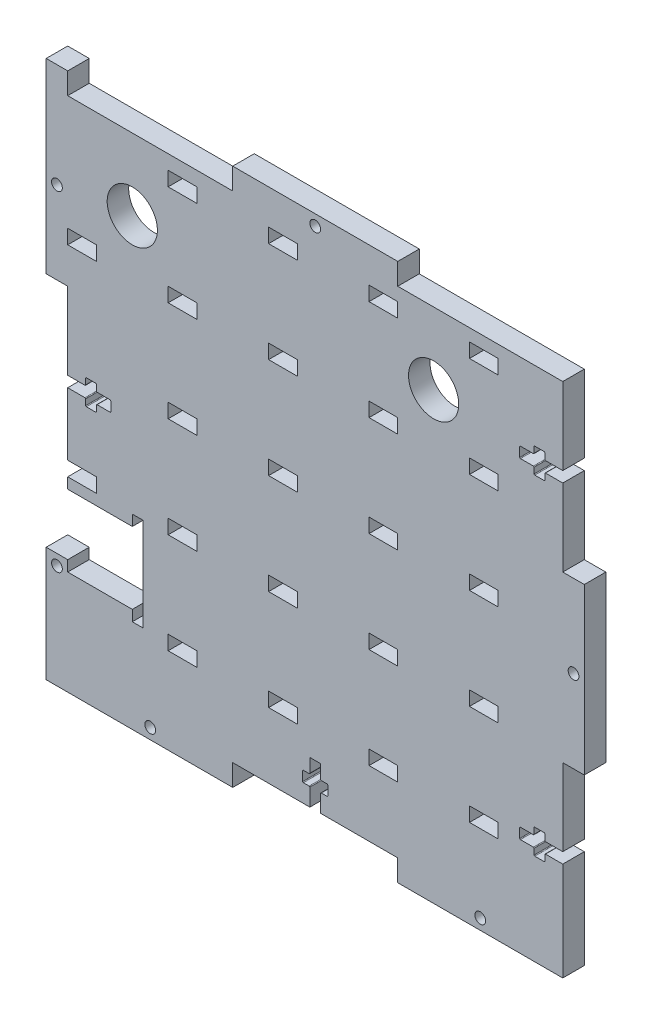
SolidWorks part; units mm, degrees
ref_plane "Front Plane" through (0, 0, 0) normal (0, 0, 1) x (1, 0, 0)
ref_plane "Top Plane" through (0, 0, 0) normal (0, 1, 0) x (1, 0, 0)
ref_plane "Right Plane" through (0, 0, 0) normal (1, 0, 0) x (0, 0, -1)
sketch "Sketch1" plane through (0, 0, 0) normal (0, 0, 1) x (1, 0, 0)
  line L0 (-69, 69) -> (-23, 69)
  line L5 (-75, -75) -> (75, -75) construction
  line L6 (-75, -75) -> (-75, 75) construction
  line L7 (-75, 75) -> (75, 75) construction
  line L8 (75, -75) -> (75, 75) construction
  line L9 (75, 23) -> (69, 23)
  line L10 (69, -23) -> (75, -23)
  line L11 (-69, -69) -> (69, -69) construction
  line L12 (-69, -69) -> (-69, 69) construction
  line L13 (-69, 69) -> (69, 69) construction
  line L14 (69, -69) -> (69, 69) construction
  line L15 (-69, -69) -> (69, 69) construction
  line L16 (69, -69) -> (69, -23)
  line L17 (-23, 69) -> (-23, 75)
  line L18 (-23, 75) -> (23, 75)
  line L19 (23, 75) -> (23, 69)
  line L20 (23, 69) -> (69, 69)
  line L21 (75, -23) -> (75, 23)
  line L22 (69, 23) -> (69, 69)
  line L23 (-75, 23) -> (-69, 23)
  line L24 (-69, 69) -> (-75, 69)
  line L25 (-75, 69) -> (-75, 23)
  line L26 (69, -69) -> (69, -75)
  line L27 (69, -75) -> (23, -75)
  line L28 (23, -75) -> (23, -69)
  line L29 (23, -69) -> (-23, -69)
  line L30 (-23, -69) -> (-23, -75)
  line L31 (-23, -75) -> (-69, -75)
  line L32 (-69, -75) -> (-69, -69) construction
  line L33 (-69, 23) -> (-69, -23)
  line L34 (-69, -23) -> (-75, -23)
  line L35 (-75, -23) -> (-75, -69)
  line L36 (-75, -69) -> (-69, -69) construction
  line L37 (-46, 69) -> (-46, -75) construction
  line L38 (-69, 69) -> (69, -69) construction
  line L39 (-75, -75) -> (-69, -75)
  line L40 (-75, -75) -> (-75, -69)
  point P0 (0, 0)
  point P6 (-7, -7)
  point P26 (0, -75)
  point P27 (-75, 0)
  dimension "D1" = 150
  dimension "D2" = 150
  dimension "D5" = 46
  dimension "D3" = 6
  dimension "D6" = 6
  dimension "D7" = 6
extrude "Box Side" add sketch "Sketch1" along normal blind 6
sketch "Sketch2" plane through (0, 0, 6) normal (0, 0, 1) x (1, 0, 0)
  line L0 (23, 72) -> (-23, 72) construction
  line L1 (23, 75) -> (23, 69) construction
  line L2 (-23, 69) -> (-23, 75) construction
  line L3 (-46, 69) -> (-46, -75) construction
  line L5 (0, 75) -> (0, 69) construction
  line L6 (-23, 75) -> (23, 75) construction
  line L7 (-69, 69) -> (69, 69) construction
  line L16 (-46, 69) -> (-46, -75) construction
  line L21 (0, -69) -> (0, 69) construction
  line L35 (-69, 69) -> (-23, 69) construction
  line L36 (-44.5, 69) -> (-44.5, 64.2) construction
  line L37 (-44.3, 64) -> (-42.7, 64) construction
  line L38 (-42.5, 63.8) -> (-42.5, 61.2) construction
  line L39 (-42.7, 61) -> (-44.3, 61) construction
  line L40 (-44.5, 60.8) -> (-44.5, 57.2) construction
  line L46 (-44.7, 57) -> (-47.3, 57) construction
  line L48 (-44.5, 69) -> (-47.5, 69) construction
  line L51 (-47.5, 60.8) -> (-47.5, 57.2) construction
  line L52 (-49.3, 61) -> (-47.7, 61) construction
  line L53 (-49.5, 63.8) -> (-49.5, 61.2) construction
  line L54 (-47.7, 64) -> (-49.3, 64) construction
  line L55 (-47.5, 69) -> (-47.5, 64.2) construction
  line L56 (47.5, 69) -> (47.5, 64.2) construction
  line L57 (47.7, 64) -> (49.3, 64) construction
  line L58 (49.5, 63.8) -> (49.5, 61.2) construction
  line L59 (49.3, 61) -> (47.7, 61) construction
  line L60 (47.5, 60.8) -> (47.5, 57.2) construction
  line L61 (44.5, 69) -> (47.5, 69) construction
  line L62 (44.7, 57) -> (47.3, 57) construction
  line L63 (44.5, 60.8) -> (44.5, 57.2) construction
  line L64 (42.7, 61) -> (44.3, 61) construction
  line L65 (42.5, 63.8) -> (42.5, 61.2) construction
  line L66 (44.3, 64) -> (42.7, 64) construction
  line L67 (44.5, 69) -> (44.5, 64.2) construction
  line L68 (-69, -69) -> (69, 69) construction
  line L69 (-69, -69) -> (69, 69) construction
  line L70 (75, 0) -> (69, 0) construction
  line L71 (72, 23) -> (72, -23) construction
  line L72 (69, 44.5) -> (64.2, 44.5)
  line L73 (64, 44.3) -> (64, 42.7)
  line L74 (63.8, 42.5) -> (61.2, 42.5)
  line L75 (61, 42.7) -> (61, 44.3)
  line L76 (60.8, 44.5) -> (57.2, 44.5)
  line L77 (57, 44.7) -> (57, 47.3)
  line L78 (69, 44.5) -> (69, 47.5)
  line L79 (60.8, 47.5) -> (57.2, 47.5)
  line L80 (61, 49.3) -> (61, 47.7)
  line L81 (63.8, 49.5) -> (61.2, 49.5)
  line L82 (64, 47.7) -> (64, 49.3)
  line L83 (69, 47.5) -> (64.2, 47.5)
  line L84 (69, -47.5) -> (64.2, -47.5)
  line L85 (64, -47.7) -> (64, -49.3)
  line L86 (63.8, -49.5) -> (61.2, -49.5)
  line L87 (61, -49.3) -> (61, -47.7)
  line L88 (60.8, -47.5) -> (57.2, -47.5)
  line L89 (69, -44.5) -> (69, -47.5)
  line L90 (57, -44.7) -> (57, -47.3)
  line L91 (60.8, -44.5) -> (57.2, -44.5)
  line L92 (61, -42.7) -> (61, -44.3)
  line L93 (63.8, -42.5) -> (61.2, -42.5)
  line L94 (64, -44.3) -> (64, -42.7)
  line L95 (69, -44.5) -> (64.2, -44.5)
  line L120 (-69, 69) -> (69, -69) construction
  line L121 (-69, 69) -> (69, -69) construction
  line L122 (-1.5, -69) -> (1.5, -69)
  line L123 (-23, -69) -> (23, -69) construction
  line L124 (1.5, -69) -> (1.5, -64.2)
  line L125 (1.7, -64) -> (3.3, -64)
  line L126 (3.5, -63.8) -> (3.5, -61.2)
  line L127 (3.3, -61) -> (1.7, -61)
  line L128 (1.5, -60.8) -> (1.5, -57.2)
  line L129 (1.3, -57) -> (-1.3, -57)
  line L130 (-1.5, -60.8) -> (-1.5, -57.2)
  line L131 (-3.3, -61) -> (-1.7, -61)
  line L132 (-3.5, -63.8) -> (-3.5, -61.2)
  line L133 (-1.7, -64) -> (-3.3, -64)
  line L134 (-1.5, -69) -> (-1.5, -64.2)
  line L135 (-69, -1.5) -> (-64.2, -1.5)
  line L136 (-64, -1.7) -> (-64, -3.3)
  line L137 (-63.8, -3.5) -> (-61.2, -3.5)
  line L138 (-61, -3.3) -> (-61, -1.7)
  line L139 (-60.8, -1.5) -> (-57.2, -1.5)
  line L140 (-57, 1.3) -> (-57, -1.3)
  line L141 (-60.8, 1.5) -> (-57.2, 1.5)
  line L142 (-61, 3.3) -> (-61, 1.7)
  line L143 (-63.8, 3.5) -> (-61.2, 3.5)
  line L144 (-64, 1.7) -> (-64, 3.3)
  line L145 (-69, 1.5) -> (-64.2, 1.5)
  line L146 (-69, -1.5) -> (-69, 1.5)
  line L147 (-69, -72) -> (-23, -72) construction
  line L148 (-23, 69) -> (-75, 69) construction
  line L149 (-23, -75) -> (-23, -69) construction
  line L150 (-69, -69) -> (-69, -75) construction
  line L151 (-75, -75) -> (-23, -75) construction
  circle A0 centre (0, 72) radius 1.5
  arc A1 (-44.5, 57.2) -> (-44.7, 57) centre (-44.7, 57.2) cw construction
  arc A2 (-44.3, 61) -> (-44.5, 60.8) centre (-44.3, 60.8) ccw construction
  arc A3 (-42.5, 61.2) -> (-42.7, 61) centre (-42.7, 61.2) cw construction
  arc A4 (-42.7, 64) -> (-42.5, 63.8) centre (-42.7, 63.8) cw construction
  arc A5 (-44.5, 64.2) -> (-44.3, 64) centre (-44.3, 64.2) ccw construction
  arc A6 (-47.5, 64.2) -> (-47.7, 64) centre (-47.7, 64.2) cw construction
  arc A7 (-49.3, 64) -> (-49.5, 63.8) centre (-49.3, 63.8) ccw construction
  arc A8 (-49.5, 61.2) -> (-49.3, 61) centre (-49.3, 61.2) ccw construction
  arc A9 (-47.7, 61) -> (-47.5, 60.8) centre (-47.7, 60.8) cw construction
  arc A10 (-47.5, 57.2) -> (-47.3, 57) centre (-47.3, 57.2) ccw construction
  arc A11 (47.5, 57.2) -> (47.3, 57) centre (47.3, 57.2) cw construction
  arc A12 (47.7, 61) -> (47.5, 60.8) centre (47.7, 60.8) ccw construction
  arc A13 (49.5, 61.2) -> (49.3, 61) centre (49.3, 61.2) cw construction
  arc A14 (49.3, 64) -> (49.5, 63.8) centre (49.3, 63.8) cw construction
  arc A15 (47.5, 64.2) -> (47.7, 64) centre (47.7, 64.2) ccw construction
  arc A16 (44.5, 64.2) -> (44.3, 64) centre (44.3, 64.2) cw construction
  arc A17 (42.7, 64) -> (42.5, 63.8) centre (42.7, 63.8) ccw construction
  arc A18 (42.5, 61.2) -> (42.7, 61) centre (42.7, 61.2) ccw construction
  arc A19 (44.3, 61) -> (44.5, 60.8) centre (44.3, 60.8) cw construction
  arc A20 (44.5, 57.2) -> (44.7, 57) centre (44.7, 57.2) ccw construction
  arc A21 (57.2, 44.5) -> (57, 44.7) centre (57.2, 44.7) cw
  arc A22 (61, 44.3) -> (60.8, 44.5) centre (60.8, 44.3) ccw
  arc A23 (61.2, 42.5) -> (61, 42.7) centre (61.2, 42.7) cw
  arc A24 (64, 42.7) -> (63.8, 42.5) centre (63.8, 42.7) cw
  arc A25 (64.2, 44.5) -> (64, 44.3) centre (64.2, 44.3) ccw
  arc A26 (64.2, 47.5) -> (64, 47.7) centre (64.2, 47.7) cw
  arc A27 (64, 49.3) -> (63.8, 49.5) centre (63.8, 49.3) ccw
  arc A28 (61.2, 49.5) -> (61, 49.3) centre (61.2, 49.3) ccw
  arc A29 (61, 47.7) -> (60.8, 47.5) centre (60.8, 47.7) cw
  arc A30 (57.2, 47.5) -> (57, 47.3) centre (57.2, 47.3) ccw
  arc A31 (57.2, -47.5) -> (57, -47.3) centre (57.2, -47.3) cw
  arc A32 (61, -47.7) -> (60.8, -47.5) centre (60.8, -47.7) ccw
  arc A33 (61.2, -49.5) -> (61, -49.3) centre (61.2, -49.3) cw
  arc A34 (64, -49.3) -> (63.8, -49.5) centre (63.8, -49.3) cw
  arc A35 (64.2, -47.5) -> (64, -47.7) centre (64.2, -47.7) ccw
  arc A36 (64.2, -44.5) -> (64, -44.3) centre (64.2, -44.3) cw
  arc A37 (64, -42.7) -> (63.8, -42.5) centre (63.8, -42.7) ccw
  arc A38 (61.2, -42.5) -> (61, -42.7) centre (61.2, -42.7) ccw
  arc A39 (61, -44.3) -> (60.8, -44.5) centre (60.8, -44.3) cw
  arc A40 (57.2, -44.5) -> (57, -44.7) centre (57.2, -44.7) ccw
  circle A41 centre (72, 0) radius 1.5
  arc A62 (1.5, -57.2) -> (1.3, -57) centre (1.3, -57.2) ccw
  arc A63 (1.7, -61) -> (1.5, -60.8) centre (1.7, -60.8) cw
  arc A64 (3.5, -61.2) -> (3.3, -61) centre (3.3, -61.2) ccw
  arc A65 (3.3, -64) -> (3.5, -63.8) centre (3.3, -63.8) ccw
  arc A66 (1.5, -64.2) -> (1.7, -64) centre (1.7, -64.2) cw
  arc A67 (-1.5, -64.2) -> (-1.7, -64) centre (-1.7, -64.2) ccw
  arc A68 (-3.3, -64) -> (-3.5, -63.8) centre (-3.3, -63.8) cw
  arc A69 (-3.5, -61.2) -> (-3.3, -61) centre (-3.3, -61.2) cw
  arc A70 (-1.7, -61) -> (-1.5, -60.8) centre (-1.7, -60.8) ccw
  arc A71 (-1.5, -57.2) -> (-1.3, -57) centre (-1.3, -57.2) cw
  arc A72 (-57.2, -1.5) -> (-57, -1.3) centre (-57.2, -1.3) ccw
  arc A73 (-61, -1.7) -> (-60.8, -1.5) centre (-60.8, -1.7) cw
  arc A74 (-61.2, -3.5) -> (-61, -3.3) centre (-61.2, -3.3) ccw
  arc A75 (-64, -3.3) -> (-63.8, -3.5) centre (-63.8, -3.3) ccw
  arc A76 (-64.2, -1.5) -> (-64, -1.7) centre (-64.2, -1.7) cw
  arc A77 (-64.2, 1.5) -> (-64, 1.7) centre (-64.2, 1.7) ccw
  arc A78 (-64, 3.3) -> (-63.8, 3.5) centre (-63.8, 3.3) cw
  arc A79 (-61.2, 3.5) -> (-61, 3.3) centre (-61.2, 3.3) cw
  arc A80 (-61, 1.7) -> (-60.8, 1.5) centre (-60.8, 1.7) ccw
  arc A81 (-57.2, 1.5) -> (-57, 1.3) centre (-57.2, 1.3) cw
  circle A82 centre (-46, -72) radius 1.5
  circle A83 centre (46, -72) radius 1.5
  circle A84 centre (-72, 46) radius 1.5
  circle A85 centre (-72, -46) radius 1.5
  point P6 (0, 72)
  point P38 (0, 0)
  point P56 (-46, 57)
  point P88 (46, 57)
  point P161 (57, 46)
  point P162 (57, -46)
  point P198 (0, -57)
  point P231 (-57, 0)
  point P234 (-42.5, 62.5)
  dimension "D1" = 3
  dimension "D2" = 0.2
  dimension "D8" = 0.2
  dimension "D14" = 3
  dimension "D4" = 3
  dimension "D7" = 1.5
  dimension "D10" = 3
  dimension "D12" = 1.5
  dimension "D9" = 12
  dimension "D11" = 5
  dimension "D13" = 7
  dimension "D3" = 12
  dimension "D5" = 7
  dimension "D6" = 5
extrude "Screw Cut-outs" cut sketch "Sketch2" against normal through all
sketch "Sketch3" plane through (0, 0, 6) normal (0, 0, 1) x (1, 0, 0)
  line L0 (-75, -75) -> (-23, -75) construction
  line L1 (-75, -49) -> (-48, -49)
  line L2 (-75, -49) -> (-75, -23)
  line L3 (-75, -23) -> (-48, -23)
  line L4 (-48, -49) -> (-48, -23)
  line L5 (-75, -23) -> (-75, -75) construction
  line L6 (-75, -46) -> (-48, -46)
  line L7 (-75, -26) -> (-48, -26)
  line L9 (-75, -26) -> (-69, -26)
  line L10 (-75, -26) -> (-75, -29)
  line L11 (-75, -29) -> (-69, -29)
  line L12 (-69, -26) -> (-69, -29)
  line L13 (-75, -46) -> (-69, -46)
  line L14 (-75, -46) -> (-75, -43)
  line L15 (-75, -43) -> (-69, -43)
  line L16 (-69, -46) -> (-69, -43)
  line L17 (-69, -26) -> (-75, -26)
  line L18 (-69, -26) -> (-69, -23)
  line L19 (-69, -23) -> (-75, -23)
  line L20 (-75, -26) -> (-75, -23)
  line L25 (-48, -23) -> (-51, -23)
  line L26 (-48, -23) -> (-48, -26)
  line L27 (-48, -26) -> (-51, -26)
  line L28 (-51, -23) -> (-51, -26)
  line L29 (-48, -46) -> (-51, -46)
  line L30 (-48, -46) -> (-48, -49)
  line L31 (-48, -49) -> (-51, -49)
  line L32 (-51, -46) -> (-51, -49)
  dimension "D1" = 26
  dimension "D2" = 27
  dimension "D3" = 26
  dimension "D4" = 20
  dimension "D5" = 3
  dimension "D6" = 3
  dimension "D7" = 6
  dimension "D8" = 3
  dimension "D9" = 3
extrude "Cut-Extrude1" cut sketch "Sketch3" against normal through all contours L7 L2 L6 L4 | L10 L9 L12 L11 | L18 L17 L20 L19 | L26 L25 L28 L27 | L30 L29 L32 L31 region at (-60.75, -36, 6)
sketch "Sketch4" plane through (0, 0, 6) normal (0, 0, 1) x (1, 0, 0)
  line L0 (-33, 65) -> (-33, 61)
  line L1 (-69, 65) -> (-61, 65) construction
  line L2 (-69, 65) -> (-69, 61) construction
  line L3 (-69, 61) -> (-61, 61) construction
  line L4 (-61, 65) -> (-61, 61) construction
  line L5 (-65, 63) -> (-37, 63) construction
  line L6 (-65, 63) -> (-65, 35) construction
  line L7 (-65, 35) -> (-37, 35) construction
  line L8 (-37, 63) -> (-37, 35) construction
  line L9 (-65, 63) -> (-37, 35) construction
  line L10 (-65, 35) -> (-37, 63) construction
  line L11 (-41, 65) -> (-33, 65)
  line L12 (-41, 65) -> (-41, 61)
  line L13 (-41, 61) -> (-33, 61)
  line L14 (-33, 37) -> (-33, 33)
  line L15 (-41, 37) -> (-33, 37)
  line L16 (-41, 37) -> (-41, 33)
  line L17 (-41, 33) -> (-33, 33)
  line L18 (-61, 37) -> (-61, 33)
  line L19 (-69, 37) -> (-61, 37)
  line L20 (-69, 37) -> (-69, 33)
  line L21 (-69, 33) -> (-61, 33)
  line L22 (-23, 69) -> (-75, 69) construction
  line L23 (-75, 69) -> (-75, 23) construction
  line L24 (15, 33.2836) -> (23, 33.2836)
  line L25 (15, 37.2836) -> (23, 37.2836)
  line L26 (15, 37.2836) -> (15, 33.2836)
  line L27 (23, 37.2836) -> (23, 33.2836)
  line L28 (-5, 37.2836) -> (-5, 33.2836)
  line L29 (-13, 33.2836) -> (-5, 33.2836)
  line L30 (-13, 37.2836) -> (-13, 33.2836)
  line L31 (-13, 37.2836) -> (-5, 37.2836)
  line L32 (-13, 61.2836) -> (-5, 61.2836)
  line L33 (-13, 65.2836) -> (-13, 61.2836)
  line L34 (-13, 65.2836) -> (-5, 65.2836)
  line L35 (-5, 65.2836) -> (-5, 61.2836)
  line L36 (23, 65.2836) -> (23, 61.2836)
  line L37 (15, 61.2836) -> (23, 61.2836)
  line L38 (15, 65.2836) -> (23, 65.2836)
  line L39 (15, 65.2836) -> (15, 61.2836)
  line L44 (51, 37.5671) -> (51, 33.5671)
  line L45 (43, 33.5671) -> (51, 33.5671)
  line L46 (43, 37.5671) -> (43, 33.5671)
  line L47 (43, 37.5671) -> (51, 37.5671)
  line L48 (43, 61.5671) -> (51, 61.5671)
  line L49 (43, 65.5671) -> (43, 61.5671)
  line L50 (43, 65.5671) -> (51, 65.5671)
  line L51 (51, 65.5671) -> (51, 61.5671)
  line L56 (15, -22.7164) -> (23, -22.7164)
  line L57 (15, -18.7164) -> (23, -18.7164)
  line L58 (15, -18.7164) -> (15, -22.7164)
  line L59 (23, -18.7164) -> (23, -22.7164)
  line L60 (-5, -18.7164) -> (-5, -22.7164)
  line L61 (-13, -22.7164) -> (-5, -22.7164)
  line L62 (-13, -18.7164) -> (-13, -22.7164)
  line L63 (-13, -18.7164) -> (-5, -18.7164)
  line L64 (-13, 5.2836) -> (-5, 5.2836)
  line L65 (-13, 9.2836) -> (-13, 5.2836)
  line L66 (-13, 9.2836) -> (-5, 9.2836)
  line L67 (-5, 9.2836) -> (-5, 5.2836)
  line L68 (23, 9.2836) -> (23, 5.2836)
  line L69 (15, 5.2836) -> (23, 5.2836)
  line L70 (15, 9.2836) -> (23, 9.2836)
  line L71 (15, 9.2836) -> (15, 5.2836)
  line L76 (51, -18.4329) -> (51, -22.4329)
  line L77 (43, -22.4329) -> (51, -22.4329)
  line L78 (43, -18.4329) -> (43, -22.4329)
  line L79 (43, -18.4329) -> (51, -18.4329)
  line L80 (43, 5.5671) -> (51, 5.5671)
  line L81 (43, 9.5671) -> (43, 5.5671)
  line L82 (43, 9.5671) -> (51, 9.5671)
  line L83 (51, 9.5671) -> (51, 5.5671)
  line L96 (-13, -50.7164) -> (-5, -50.7164)
  line L97 (-13, -46.7164) -> (-13, -50.7164)
  line L98 (-13, -46.7164) -> (-5, -46.7164)
  line L99 (-5, -46.7164) -> (-5, -50.7164)
  line L100 (23, -46.7164) -> (23, -50.7164)
  line L101 (15, -50.7164) -> (23, -50.7164)
  line L102 (15, -46.7164) -> (23, -46.7164)
  line L103 (15, -46.7164) -> (15, -50.7164)
  line L112 (43, -50.4329) -> (51, -50.4329)
  line L113 (43, -46.4329) -> (43, -50.4329)
  line L114 (43, -46.4329) -> (51, -46.4329)
  line L115 (51, -46.4329) -> (51, -50.4329)
  line L120 (-41, -23) -> (-33, -23)
  line L121 (-41, -19) -> (-33, -19)
  line L122 (-41, -19) -> (-41, -23)
  line L123 (-33, -19) -> (-33, -23)
  line L124 (-61, -19) -> (-61, -23)
  line L125 (-69, -23) -> (-61, -23)
  line L126 (-69, -19) -> (-69, -23)
  line L127 (-69, -19) -> (-61, -19)
  line L128 (-69, 5) -> (-61, 5) construction
  line L129 (-69, 9) -> (-69, 5) construction
  line L130 (-69, 9) -> (-61, 9) construction
  line L131 (-61, 9) -> (-61, 5) construction
  line L132 (-33, 9) -> (-33, 5)
  line L133 (-41, 5) -> (-33, 5)
  line L134 (-41, 9) -> (-33, 9)
  line L135 (-41, 9) -> (-41, 5)
  line L144 (-69, -51) -> (-61, -51) construction
  line L145 (-69, -47) -> (-69, -51) construction
  line L146 (-69, -47) -> (-61, -47) construction
  line L147 (-61, -47) -> (-61, -51) construction
  line L148 (-33, -47) -> (-33, -51)
  line L149 (-41, -51) -> (-33, -51)
  line L150 (-41, -47) -> (-33, -47)
  line L151 (-41, -47) -> (-41, -51)
  line L152 (15, -78.7164) -> (23, -78.7164) [skipped]
  line L153 (15, -74.7164) -> (23, -74.7164) [skipped]
  line L154 (15, -74.7164) -> (15, -78.7164) [skipped]
  line L155 (23, -74.7164) -> (23, -78.7164) [skipped]
  line L156 (-5, -74.7164) -> (-5, -78.7164) [skipped]
  line L157 (-13, -78.7164) -> (-5, -78.7164) [skipped]
  line L158 (-13, -74.7164) -> (-13, -78.7164) [skipped]
  line L159 (-13, -74.7164) -> (-5, -74.7164) [skipped]
  line L160 (71, -78.4329) -> (79, -78.4329) [skipped]
  line L161 (71, -74.4329) -> (79, -74.4329) [skipped]
  line L162 (71, -74.4329) -> (71, -78.4329) [skipped]
  line L163 (79, -74.4329) -> (79, -78.4329) [skipped]
  line L164 (51, -74.4329) -> (51, -78.4329) [skipped]
  line L165 (43, -78.4329) -> (51, -78.4329) [skipped]
  line L166 (43, -74.4329) -> (43, -78.4329) [skipped]
  line L167 (43, -74.4329) -> (51, -74.4329) [skipped]
  line L168 (-41, -79) -> (-33, -79) [skipped]
  line L169 (-41, -75) -> (-33, -75) [skipped]
  line L170 (-41, -75) -> (-41, -79) [skipped]
  line L171 (-33, -75) -> (-33, -79) [skipped]
  line L172 (-61, -75) -> (-61, -79) [skipped]
  line L173 (-69, -79) -> (-61, -79) [skipped]
  line L174 (-69, -75) -> (-69, -79) [skipped]
  line L175 (-69, -75) -> (-61, -75) [skipped]
  line L176 (71, 33.5671) -> (79, 33.5671) [skipped]
  line L177 (71, 37.5671) -> (79, 37.5671) [skipped]
  line L178 (71, 37.5671) -> (71, 33.5671) [skipped]
  line L179 (79, 37.5671) -> (79, 33.5671) [skipped]
  line L180 (79, 65.5671) -> (79, 61.5671) [skipped]
  line L181 (71, 61.5671) -> (79, 61.5671) [skipped]
  line L182 (71, 65.5671) -> (79, 65.5671) [skipped]
  line L183 (71, 65.5671) -> (71, 61.5671) [skipped]
  line L184 (71, -22.4329) -> (79, -22.4329) [skipped]
  line L185 (71, -18.4329) -> (79, -18.4329) [skipped]
  line L186 (71, -18.4329) -> (71, -22.4329) [skipped]
  line L187 (79, -18.4329) -> (79, -22.4329) [skipped]
  line L188 (79, 9.5671) -> (79, 5.5671) [skipped]
  line L189 (71, 5.5671) -> (79, 5.5671) [skipped]
  line L190 (71, 9.5671) -> (79, 9.5671) [skipped]
  line L191 (71, 9.5671) -> (71, 5.5671) [skipped]
  line L192 (79, -46.4329) -> (79, -50.4329) [skipped]
  line L193 (71, -50.4329) -> (79, -50.4329) [skipped]
  line L194 (71, -46.4329) -> (79, -46.4329) [skipped]
  line L195 (71, -46.4329) -> (71, -50.4329) [skipped]
  circle A0 centre (-65, 63) radius 2 construction
  point P6 (-65, 61)
  point P7 (-69, 35)
  point P8 (-65, 33)
  point P12 (-51, 49)
  point P13 (-37, 33)
  point P33 (-37, 61)
  point P41 (-65, 37)
  dimension "D1" = 8
  dimension "D2" = 4
  dimension "D3" = 2
  dimension "D5" = 28
  dimension "D6" = 6
  dimension "D7" = 10
  dimension "D10" = 20
  dimension "D11" = 24
  dimension "D4" = 2
  dimension "D8" = 3
  dimension "D9" = 3
extrude "Cut-Extrude2" cut sketch "Sketch4" against normal through all
sketch "Sketch5" plane through (0, 0, 6) normal (0, 0, 1) x (1, 0, 0)
  line L0 (-61, 37) -> (-69, 37) construction
  line L1 (-61, 33) -> (-61, 37) construction
  line L3 (23, 33.2836) -> (23, 37.2836) construction
  line L4 (23, 37.2836) -> (15, 37.2836) construction
  circle A0 centre (-51, 49) radius 7
  circle A1 centre (33, 49) radius 7
  point P2 (-65, 37)
  point P3 (-61, 35)
  point P6 (-65, 35)
  point P9 (19, 37.2836)
  point P10 (23, 35.2836)
  dimension "D3" = 14
  dimension "D5" = 14
  dimension "D1" = 14
  dimension "D2" = 14
  dimension "D4" = 14
extrude "Cut-Extrude3" cut sketch "Sketch5" against normal through all
sketch "Sketch6" plane through (0, 0, 6) normal (0, 0, 1) x (1, 0, 0)
  line L1 (-75, 69) -> (-69, 69)
  line L2 (-75, 69) -> (-75, 75)
  line L3 (-75, 75) -> (-69, 75)
  line L4 (-69, 69) -> (-69, 75)
  dimension "D1" = 6
  dimension "D2" = 6
extrude "Boss-Extrude1" add sketch "Sketch6" against normal blind 6
equation "\"filletRadius\"=0.2"
equation "\"D8@Sketch2\"=\"filletRadius\""
equation "\"D2@Sketch2\"=\"filletRadius\""
equation "\"fingerWidth\"= 46"
equation "\"D5@Sketch1\"=\"fingerWidth\""
equation "\"wallThickness\"= 6"
equation "\"D3@Sketch1\" = \"wallThickness\""
equation "\"D6@Sketch1\" = \"wallThickness\""
equation "\"D7@Sketch1\" = \"wallThickness\""
equation "\"D1@Box Side\" = \"wallThickness\""
equation "\"M3\"= 3"
equation "\"D14@Sketch2\"=\"M3\""
equation "\"D1@Sketch2\"=\"M3\""
equation "\"D12@Sketch2\"=\"M3\"/2"
equation "\"nutThickness\"=3"
equation "\"D10@Sketch2\" = \"nutThickness\""
equation "\"boltLength\"= 12"
equation "\"D9@Sketch2\" = \"boltLength\""
equation "\"distanceToNut\"= 5"
equation "\"D11@Sketch2\" = \"distanceToNut\""
equation "\"D13@Sketch2\" = \"nutWidth\""
equation "\"D7@Sketch2\"=\"M3\"/2"
equation "\"D4@Sketch2\" = \"nutThickness\""
equation "\"D3@Sketch2\" = \"boltLength\""
equation "\"D5@Sketch2\" = \"nutWidth\""
equation "\"D6@Sketch2\" = \"distanceToNut\""
equation "\"sideLength\"=150"
equation "\"D1@Sketch1\"=\"sideLength\""
equation "\"D2@Sketch1\"=\"sideLength\""
equation "\"nutWidth\"=7"
